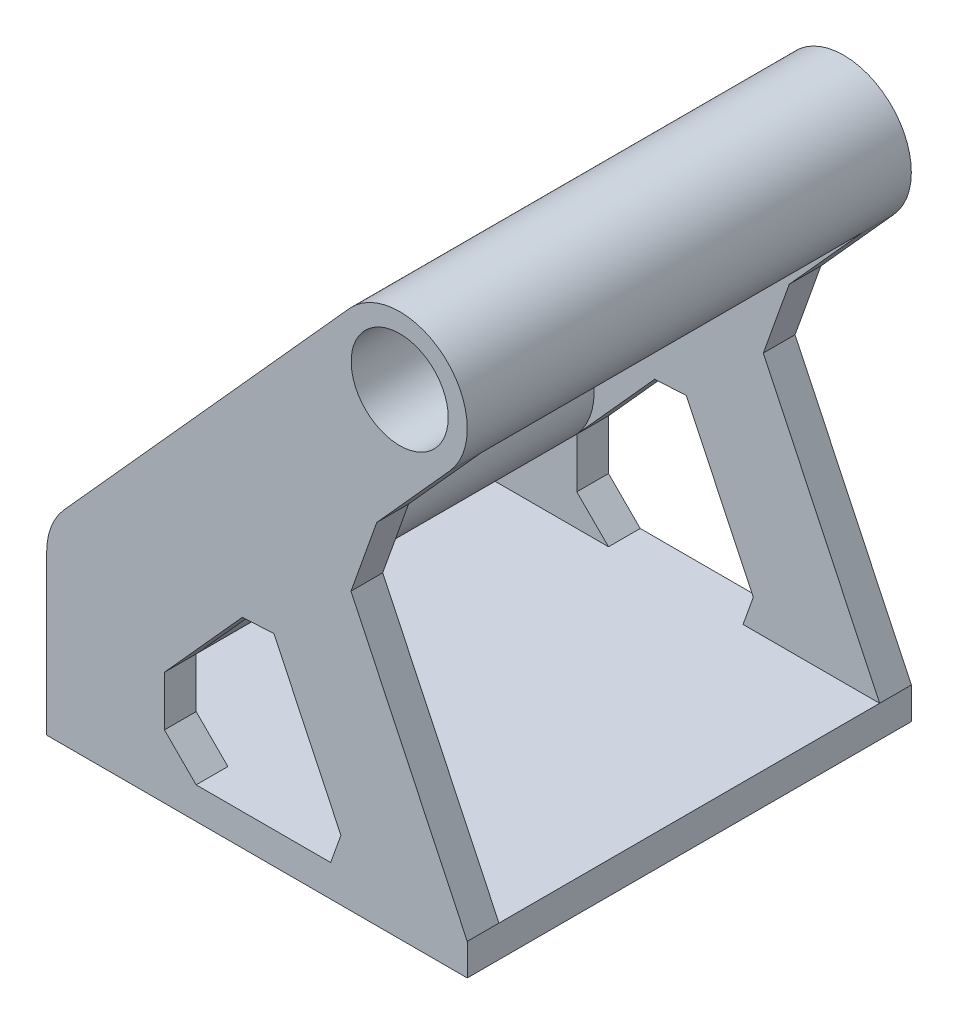
SolidWorks part; units mm, degrees
ref_plane "Front Plane" through (0, 0, 0) normal (0, 0, 1) x (1, 0, 0)
ref_plane "Top Plane" through (0, 0, 0) normal (0, 1, 0) x (1, 0, 0)
ref_plane "Right Plane" through (0, 0, 0) normal (1, 0, 0) x (0, 0, -1)
sketch "Sketch1" plane through (0, 0, 0) normal (0, 0, 1) x (1, 0, 0)
  line L0 (-7.9161, 7.1245) -> (37.0839, 57.1245)
  line L1 (55.65, -25) -> (55.65, -20)
  line L2 (-10.65, 0) -> (-10.65, -25)
  line L3 (52.9161, 42.8755) -> (35.1787, 23.1673)
  line L4 (55.65, -20) -> (35.1787, 23.1673)
  line L5 (23.538, 10.2332) -> (7.9161, -7.1245)
  line L6 (-10.65, -25) -> (55.65, -25)
  line L7 (37.8755, -20) -> (23.538, 10.2332)
  line L9 (37.8755, -20) -> (7.9161, -20)
  line L10 (7.9161, -20) -> (7.9161, -7.1245)
  circle A0 centre (0, 0) radius 7.65
  circle A1 centre (45, 50) radius 7.65
  arc A2 (-7.9161, 7.1245) -> (-10.65, 0) centre (0, 0) ccw
  arc A4 (52.9161, 42.8755) -> (37.0839, 57.1245) centre (45, 50) ccw
  dimension "D1" = 15.3
  dimension "D5" = 5
  dimension "D2" = 45
  dimension "D3" = 50
  dimension "D6" = 25
extrude "Boss-Extrude2" add sketch "Sketch1" along normal blind 5
sketch "Sketch2" plane through (0, 0, 5) normal (0, 0, 1) x (1, 0, 0)
  circle A0 centre (45, 50) radius 7.65
  circle A1 centre (45, 50) radius 10.65
extrude "Boss-Extrude3" add sketch "Sketch2" along normal blind 60
sketch "Sketch3" plane through (0, 0, 5) normal (0, 0, 1) x (1, 0, 0)
  line L1 (-10.65, -25) -> (55.65, -25)
  line L2 (-10.65, -25) -> (-10.65, -20)
  line L5 (-10.65, -20) -> (55.65, -20)
  line L6 (55.65, -25) -> (55.65, -20)
  circle A0 centre (0, 0) radius 7.65
  circle A1 centre (0, 0) radius 10.65
extrude "Boss-Extrude4" add sketch "Sketch3" along normal blind 60
sketch "Sketch5" plane through (0, 0, 65) normal (0, 0, 1) x (1, 0, 0)
  line L0 (-10.65, 0) -> (-10.65, -20) construction
  line L2 (7.9161, -20) -> (7.9161, -7.1245) construction
  line L3 (23.538, 10.2332) -> (37.8755, -20) construction
  line L5 (55.65, -20) -> (35.1787, 23.1673) construction
  line L6 (35.1787, 23.1673) -> (52.9161, 42.8755) construction
  line L7 (37.0839, 57.1245) -> (-7.9161, 7.1245) construction
  line L8 (7.9161, -7.1245) -> (23.538, 10.2332) construction
  line L9 (-10.65, 0) -> (-10.65, -20)
  line L10 (7.9161, -20) -> (37.8755, -20)
  line L11 (7.9161, -20) -> (7.9161, -7.1245)
  line L12 (23.538, 10.2332) -> (37.8755, -20)
  line L14 (55.65, -20) -> (35.1787, 23.1673)
  line L15 (35.1787, 23.1673) -> (52.9161, 42.8755)
  line L16 (37.0839, 57.1245) -> (-7.9161, 7.1245)
  line L17 (7.9161, -7.1245) -> (23.538, 10.2332)
  line L18 (-10.65, -20) -> (-10.65, -25)
  line L19 (-10.65, -25) -> (55.65, -25)
  line L20 (55.65, -25) -> (55.65, -20)
  arc A0 (-10.65, 0) -> (7.9161, -7.1245) centre (0, 0) ccw construction
  arc A2 (7.9161, -7.1245) -> (-7.9161, 7.1245) centre (0, 0) ccw construction
  arc A3 (-10.65, 0) -> (7.9161, -7.1245) centre (0, 0) ccw
  circle A4 centre (45, 50) radius 7.65
  arc A5 (7.9161, -7.1245) -> (-7.9161, 7.1245) centre (0, 0) ccw
  arc A6 (37.0839, 57.1245) -> (52.9161, 42.8755) centre (45, 50) cw
  arc A7 (-7.9161, 7.1245) -> (-10.65, 0) centre (0, 0) ccw
  line M2 (-10.65, -20) -> (-10.65, -25)
  line M3 (-10.65, -25) -> (55.65, -25)
  line M4 (55.65, -25) -> (55.65, -20)
  line M5 (55.65, -20) -> (-10.65, -20)
extrude "Boss-Extrude6" add sketch "Sketch5" along normal blind 5 contours A6 L16 A5 L17 L12 L14 L15 M5 | A5 A7 A3 | M5 M2 M3 M4 | A3 L9 L11 M5 region at (-1.8741, -14.2569, 65) region at (0, 0, 65) region at (22.5, -22.5, 65) region at (30.0281, 18.1895, 65)
chamfer "Chamfer1" distance 5 angle 45 2 edges at (35.1787, 23.1673, 2.5) (35.1787, 23.1673, 67.5) first distance on face at (45.4143, 1.5836, 2.5) first distance on face at (45.4143, 1.5836, 67.5)
chamfer "Chamfer2" distance 5 angle 45 2 edges at (23.538, 10.2332, 2.5) (23.538, 10.2332, 67.5) first distance on face at (15.727, 1.5544, 2.5) first distance on face at (15.727, 1.5544, 67.5)
chamfer "Chamfer3" distance 5 angle 45 4 edges at (37.8755, -20, 2.5) (7.9161, -20, 2.5) (7.9161, -20, 67.5) (37.8755, -20, 67.5) first distance on face at (31.5258, -6.6105, 2.5) first distance on face at (7.9161, -13.5622, 2.5) first distance on face at (7.9161, -13.5622, 67.5) first distance on face at (31.5258, -6.6105, 67.5)
